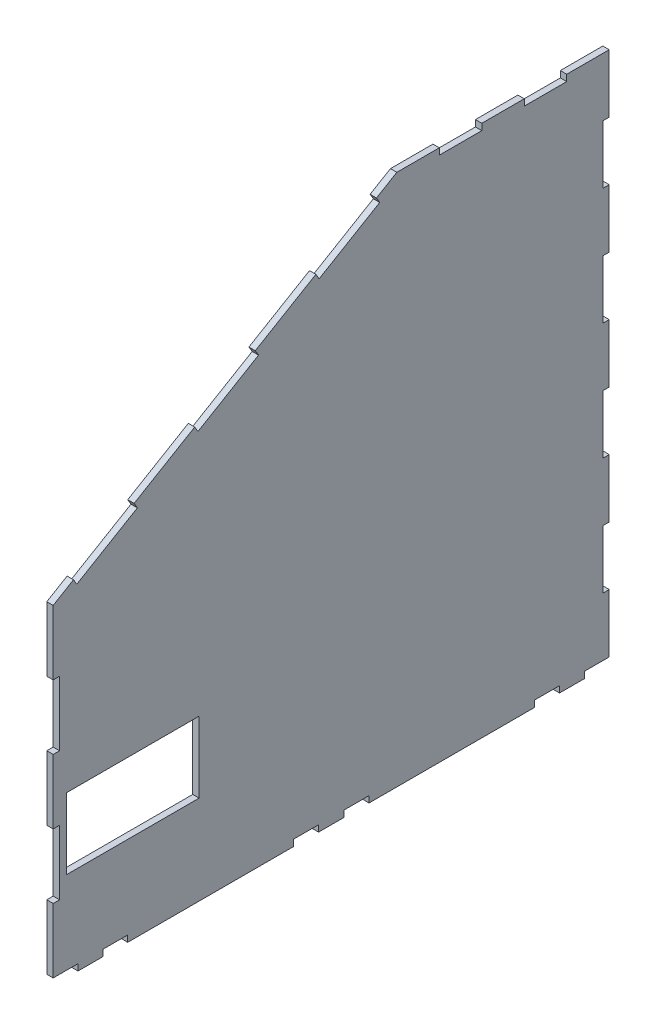
SolidWorks part; units mm, degrees
ref_plane "Ön Düzlem" through (0, 0, 0) normal (0, 0, 1) x (1, 0, 0)
ref_plane "Üst Düzlem" through (0, 0, 0) normal (0, 1, 0) x (1, 0, 0)
ref_plane "Sağ Düzlem" through (0, 0, 0) normal (1, 0, 0) x (0, 0, -1)
sketch "Sketch1" plane through (0, 0, 0) normal (1, 0, 0) x (0, 0, -1)
  line L0 (117.52, 112.5) -> (99.566, 112.5)
  line L5 (107.0133, -112.5) -> (96.5067, -112.5)
  line L6 (117.52, -109.8) -> (117.52, -85.1)
  line L14 (-6.4686, 92.2661) -> (-32.0795, 77.122)
  line L17 (27.75, 112.5) -> (19.1423, 107.4101)
  line L18 (-117.52, -109.8) -> (-107.0133, -109.8)
  line L19 (-117.52, -109.8) -> (-117.52, -82.52)
  line L21 (-96.5067, -112.5) -> (-107.0133, -112.5)
  line L22 (-114.82, -27.96) -> (-114.82, -0.68)
  line L23 (-117.52, -55.24) -> (-117.52, -27.96)
  line L25 (-117.52, -0.68) -> (-117.52, 26.6)
  line L26 (-117.52, -0.68) -> (-114.82, -0.68)
  line L27 (-117.52, -27.96) -> (-114.82, -27.96)
  line L28 (-114.82, -82.52) -> (-114.82, -55.24)
  line L29 (-117.52, -55.24) -> (-114.82, -55.24)
  line L30 (-117.52, -82.52) -> (-114.82, -82.52)
  line L31 (-86, -109.8) -> (-86, -112.5)
  line L32 (-107.0133, -109.8) -> (-107.0133, -112.5)
  line L33 (-96.5067, -109.8) -> (-96.5067, -112.5)
  line L34 (-96.5067, -109.8) -> (-86, -109.8)
  line L36 (-86, -112.5) -> (-16, -112.5)
  line L37 (-16, -112.5) -> (-16, -109.8)
  line L38 (-16, -109.8) -> (-5.3333, -109.8)
  line L40 (5.3333, -112.5) -> (-5.3333, -112.5)
  line L41 (5.3333, -109.8) -> (16, -109.8)
  line L42 (-5.3333, -109.8) -> (-5.3333, -112.5)
  line L43 (5.3333, -109.8) -> (5.3333, -112.5)
  line L44 (16, -109.8) -> (16, -112.5)
  line L47 (114.82, -35.7) -> (114.82, -11)
  line L48 (86, -109.8) -> (96.5067, -109.8)
  line L51 (86, -109.8) -> (86, -112.5)
  line L52 (96.5067, -109.8) -> (96.5067, -112.5)
  line L53 (107.0133, -109.8) -> (107.0133, -112.5)
  line L54 (86, -112.5) -> (16, -112.5)
  line L55 (107.0133, -109.8) -> (117.52, -109.8)
  line L56 (117.52, -60.4) -> (117.52, -35.7)
  line L57 (114.82, 13.7) -> (114.82, 38.4)
  line L58 (117.52, -11) -> (117.52, 13.7)
  line L59 (114.82, 63.1) -> (114.82, 87.8)
  line L60 (117.52, 38.4) -> (117.52, 63.1)
  line L62 (117.52, 87.8) -> (117.52, 112.5)
  line L63 (114.82, -85.1) -> (114.82, -60.4)
  line L64 (117.52, -85.1) -> (114.82, -85.1)
  line L65 (117.52, 13.7) -> (114.82, 13.7)
  line L66 (117.52, 87.8) -> (114.82, 87.8)
  line L67 (117.52, 63.1) -> (114.82, 63.1)
  line L68 (117.52, 38.4) -> (114.82, 38.4)
  line L69 (117.52, -11) -> (114.82, -11)
  line L70 (117.52, -35.7) -> (114.82, -35.7)
  line L71 (117.52, -60.4) -> (114.82, -60.4)
  line L72 (-57.6905, 61.978) -> (-83.3014, 46.8339)
  line L73 (-5.0944, 89.942) -> (-6.4686, 92.2661)
  line L74 (-107.538, 29.3658) -> (-81.9271, 44.5098)
  line L76 (99.566, 109.8) -> (81.612, 109.8)
  line L78 (63.658, 109.8) -> (45.704, 109.8)
  line L79 (-108.9123, 31.6899) -> (-117.52, 26.6)
  line L80 (45.704, 109.8) -> (45.704, 112.5)
  line L81 (63.658, 109.8) -> (63.658, 112.5)
  line L82 (81.612, 109.8) -> (81.612, 112.5)
  line L83 (99.566, 109.8) -> (99.566, 112.5)
  line L87 (-108.9123, 31.6899) -> (-107.538, 29.3658)
  line L88 (19.1423, 107.4101) -> (20.5165, 105.086)
  line L89 (-56.3162, 59.6539) -> (-30.7053, 74.7979)
  line L91 (-5.0944, 89.942) -> (20.5165, 105.086)
  line L92 (-30.7053, 74.7979) -> (-32.0795, 77.122)
  line L93 (-56.3162, 59.6539) -> (-57.6905, 61.978)
  line L94 (-81.9271, 44.5098) -> (-83.3014, 46.8339)
  line L95 (45.704, 112.5) -> (27.75, 112.5)
  line L97 (81.612, 112.5) -> (63.658, 112.5)
  line L103 (-114.82, -41.8) -> (-111.82, -41.8)
  line L105 (-111.82, -74.8) -> (-111.82, -44.8)
  line L109 (-111.82, -44.8) -> (-55.82, -44.8)
  line L112 (-55.82, -44.8) -> (-55.82, -74.8)
  line L114 (-55.82, -74.8) -> (-111.82, -74.8)
  point P0 (0, 0)
extrude "Boss-Extrude1" add sketch "Sketch1" along normal blind 2.7 contours L82 L97 L81 L78 L80 L95 L17 L88 L91 L73 L14 L92 L89 L93 L72 L94 L74 L87 L79 L25 L26 L22 L27 L23 L29 L28 L30 L19 L18 L32 L21 L33 L34 L31 L36 L37 L38 L42 L40 L43 L41 L44 L54 L51 L48 L52 L5 L53 region at (0, -9.6564, -12.7532)
